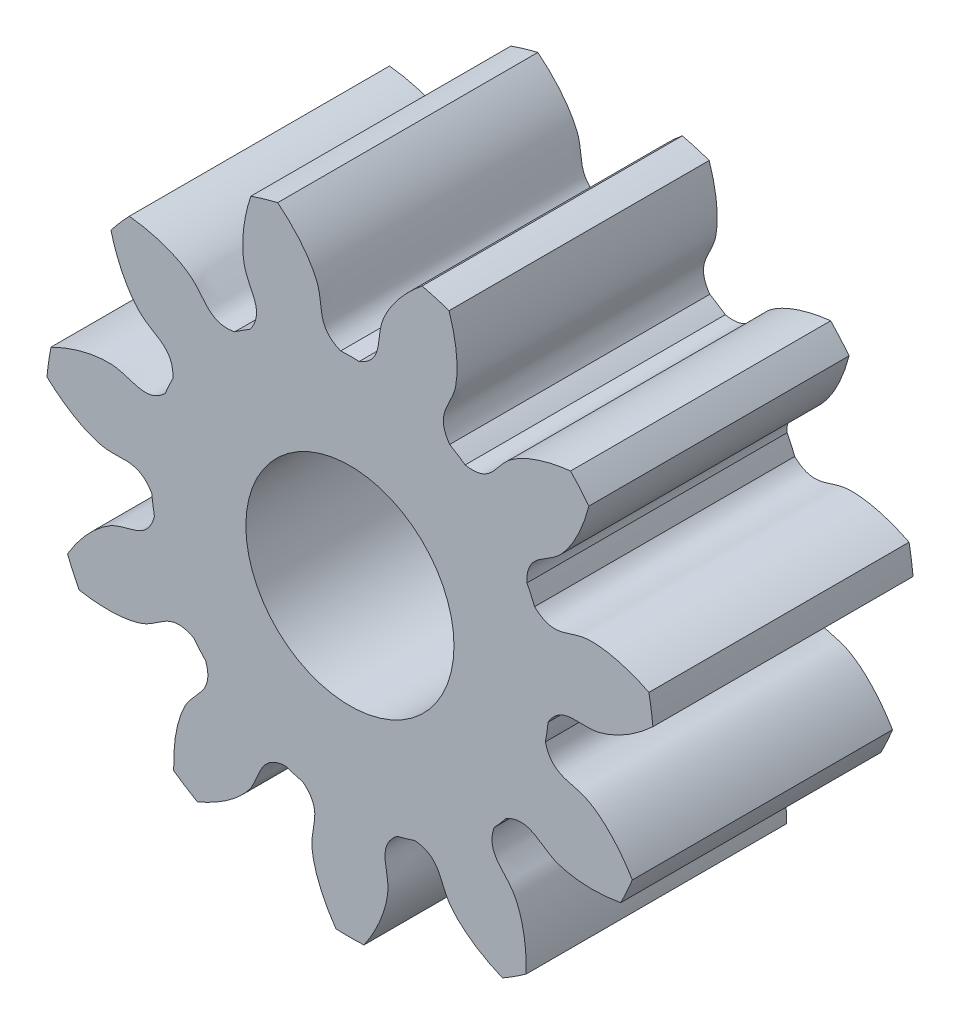
SolidWorks part; units mm, degrees
ref_plane "前视基准面" through (0, 0, 0) normal (0, 0, 1) x (1, 0, 0)
ref_plane "上视基准面" through (0, 0, 0) normal (0, 1, 0) x (1, 0, 0)
ref_plane "右视基准面" through (0, 0, 0) normal (1, 0, 0) x (0, 0, -1)
other "Configuration Table"
sketch "草图1" plane through (0, 0, 0) normal (0, 0, 1) x (1, 0, 0)
  circle A0 centre (0, 0) radius 2.925
extrude "凸台-拉伸1" add sketch "草图1" along normal blind 2.5
ref_axis "基准轴1" through (0, 0, 2.5) along (0, 0, -1)
sketch "草图2" plane through (0, 0, 0) normal (0, 0, 1) x (1, 0, 0)
  line L0 (0, 0) -> (0, 2.925) construction
  circle A0 centre (0, 0) radius 2.925 construction
  arc A1 (0.0885, 1.9104) -> (-0.0885, 1.9104) centre (0, 0) ccw
  arc A2 (1.6426, 3.2805) -> (-1.6426, 3.2805) centre (0, 0) ccw
  spline S0 degree 3 poles (0.0885, 1.9104) (0.3157, 2.001) (0.2586, 2.1861) (0.3071, 2.3434) (0.3099, 2.3518) (0.3131, 2.361) (0.3169, 2.371) (0.3212, 2.3818) (0.326, 2.3934) (0.3315, 2.4057) (0.3376, 2.4188) (0.3444, 2.4325) (0.3519, 2.447) (0.3602, 2.4621) (0.3692, 2.4779) (0.3789, 2.4942) (0.3895, 2.5112) (0.401, 2.5287) (0.4133, 2.5468) (0.4265, 2.5654) (0.4407, 2.5844) (0.4558, 2.6039) (0.4718, 2.6238) (0.4889, 2.6441) (0.5069, 2.6648) (0.526, 2.6858) (0.5462, 2.707) (0.5674, 2.7286) (0.5898, 2.7503) (0.6132, 2.7722) (0.6378, 2.7943) (0.6635, 2.8165) (0.6903, 2.8388) (0.7183, 2.8611) (0.7475, 2.8834) (0.7779, 2.9057) (0.8095, 2.9279) (0.8423, 2.9499) (0.8764, 2.9718) (0.9116, 2.9936) (0.9481, 3.015) (0.9858, 3.0363) (1.0247, 3.0571) (1.0649, 3.0777) (1.1063, 3.0978) (1.149, 3.1175) (1.1929, 3.1367) (1.238, 3.1554) (1.2844, 3.1735) (1.332, 3.191) (1.3808, 3.2078) (1.4308, 3.224) (1.482, 3.2394) (1.5525, 3.2591) (1.6063, 3.2723) (1.6426, 3.2805) knots 0 0 0 0 0.219011 0.222642 0.226699 0.231184 0.236096 0.241435 0.247201 0.253394 0.260015 0.267062 0.274537 0.282438 0.290767 0.299523 0.308706 0.318316 0.328354 0.338818 0.34971 0.361028 0.372774 0.384947 0.397547 0.410574 0.424029 0.43791 0.452219 0.466954 0.482117 0.497707 0.513724 0.530168 0.547039 0.564338 0.582063 0.600216 0.618795 0.637802 0.657236 0.677097 0.697385 0.718101 0.739243 0.760813 0.782809 0.805233 0.828084 0.851362 0.875067 0.8992 0.923759 0.948746 1 1 1 1
  spline S1 degree 3 poles (-0.0885, 1.9104) (-0.3157, 2.001) (-0.2586, 2.1861) (-0.3071, 2.3434) (-0.3099, 2.3518) (-0.3131, 2.361) (-0.3169, 2.371) (-0.3212, 2.3818) (-0.326, 2.3934) (-0.3315, 2.4057) (-0.3376, 2.4188) (-0.3444, 2.4325) (-0.3519, 2.447) (-0.3602, 2.4621) (-0.3692, 2.4779) (-0.3789, 2.4942) (-0.3895, 2.5112) (-0.401, 2.5287) (-0.4133, 2.5468) (-0.4265, 2.5654) (-0.4407, 2.5844) (-0.4558, 2.6039) (-0.4718, 2.6238) (-0.4889, 2.6441) (-0.5069, 2.6648) (-0.526, 2.6858) (-0.5462, 2.707) (-0.5674, 2.7286) (-0.5898, 2.7503) (-0.6132, 2.7722) (-0.6378, 2.7943) (-0.6635, 2.8165) (-0.6903, 2.8388) (-0.7183, 2.8611) (-0.7475, 2.8834) (-0.7779, 2.9057) (-0.8095, 2.9279) (-0.8423, 2.9499) (-0.8764, 2.9718) (-0.9116, 2.9936) (-0.9481, 3.015) (-0.9858, 3.0363) (-1.0247, 3.0571) (-1.0649, 3.0777) (-1.1063, 3.0978) (-1.149, 3.1175) (-1.1929, 3.1367) (-1.238, 3.1554) (-1.2844, 3.1735) (-1.332, 3.191) (-1.3808, 3.2078) (-1.4308, 3.224) (-1.482, 3.2394) (-1.5525, 3.2591) (-1.6063, 3.2723) (-1.6426, 3.2805) knots 0 0 0 0 0.219011 0.222642 0.226699 0.231184 0.236096 0.241435 0.247201 0.253394 0.260015 0.267062 0.274537 0.282438 0.290767 0.299523 0.308706 0.318316 0.328354 0.338818 0.34971 0.361028 0.372774 0.384947 0.397547 0.410574 0.424029 0.43791 0.452219 0.466954 0.482117 0.497707 0.513724 0.530168 0.547039 0.564338 0.582063 0.600216 0.618795 0.637802 0.657236 0.677097 0.697385 0.718101 0.739243 0.760813 0.782809 0.805233 0.828084 0.851362 0.875067 0.8992 0.923759 0.948746 1 1 1 1
extrude "切除-拉伸1" cut sketch "草图2" along normal through all
pattern_circular "阵列(圆周)1" count 11 every 32.727 about axis through (0, 0, 2.5) along (0, 0, -1) of "切除-拉伸1"
sketch "草图3" plane through (0, 0, 0) normal (0, 0, 1) x (1, 0, 0)
  circle A0 centre (0, 0) radius 2.475 construction
  dimension "Dn" = 4.95
sketch "草图4" plane through (0, 0, 2.5) normal (0, 0, 1) x (1, 0, 0)
  circle A0 centre (0, 0) radius 1
  dimension "D1" = 2
extrude "切除-拉伸2" cut sketch "草图4" against normal mid plane 10
